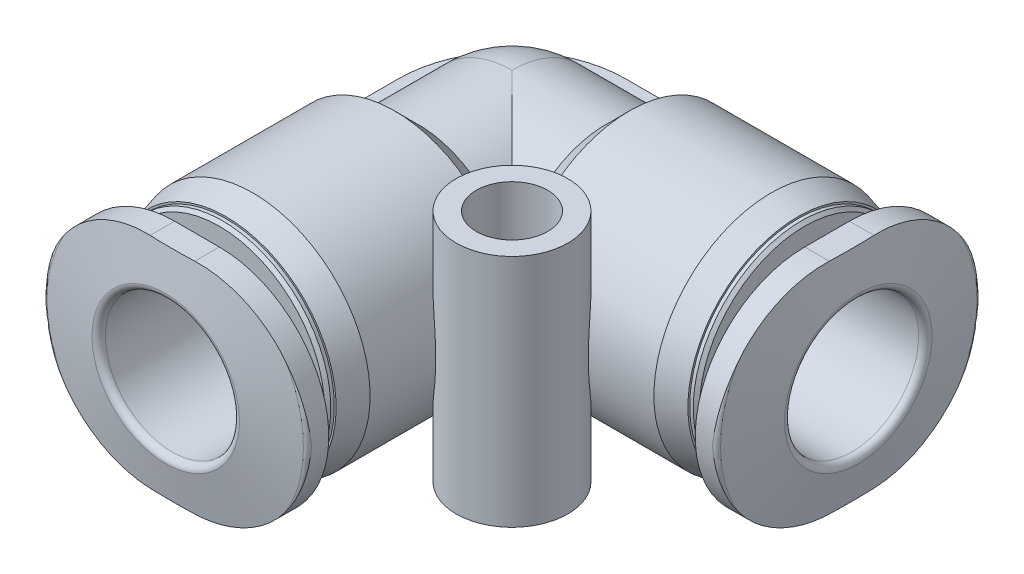
SolidWorks part; units mm, degrees
ref_plane "Ebene vorne" through (0, 0, 0) normal (0, 0, 1) x (1, 0, 0)
ref_plane "Ebene oben" through (0, 0, 0) normal (0, 1, 0) x (1, 0, 0)
ref_plane "Ebene rechts" through (0, 0, 0) normal (1, 0, 0) x (0, 0, -1)
sketch "Skizze1" plane through (0, 0, 0) normal (0, 0, 1) x (1, 0, 0)
  line L0 (0, 4.2) -> (4.2, 4.2)
  line L1 (4.2, 4.2) -> (5.25, 5.25)
  line L2 (5.25, 5.25) -> (11.6, 5.25)
  line L3 (11.6, 5.25) -> (12.8, 4.9285)
  line L4 (12.8, 4.9285) -> (12.8, 4.8481)
  line L5 (12.8, 4.8481) -> (12.9586, 4.8481)
  line L6 (12.9586, 4.8481) -> (13.1, 4.7067)
  line L7 (13.1, 4.7067) -> (13.1, 3.7)
  line L8 (13.1, 3.7) -> (13.73, 3.7)
  line L9 (14.1, 4.07) -> (14.1, 5.9)
  line L10 (14.1, 5.9) -> (14.8737, 5.9)
  line L11 (15.0707, 5.7347) -> (15.5, 3.3)
  line L12 (15.5, 3.3) -> (15.5, 0)
  line L13 (15.5, 0) -> (-4.2, 0)
  line L14 (15.5, 0) -> (-4.2, 0) construction
  arc A0 (-4.2, 0) -> (0, 4.2) centre (0, 0) cw
  arc A1 (13.73, 3.7) -> (14.1, 4.07) centre (13.73, 4.07) ccw
  arc A2 (14.8737, 5.9) -> (15.0707, 5.7347) centre (14.8737, 5.7) cw
revolve "Rotation1" add sketch "Skizze1" angle 360 about L14
ref_plane "Ebene1" through (15.5, 0, 0) normal (1, 0, 0) x (0, 0, -1)
sketch "Skizze2" plane through (15.5, 0, 0) normal (1, 0, 0) x (0, 0, -1)
  line L0 (-7.08, -4.0876) -> (0, -8.1753)
  line L1 (0, -8.1753) -> (7.08, -4.0876)
  line L2 (7.08, -4.0876) -> (7.08, 4.0876)
  line L3 (7.08, 4.0876) -> (0, 8.1753)
  line L4 (0, 8.1753) -> (-7.08, 4.0876)
  line L5 (-7.08, 4.0876) -> (-7.08, -4.0876)
  line L6 (-1, -4.9) -> (1, -4.9)
  line L7 (1, 4.9) -> (-1, 4.9)
  arc A0 (-5.9, 0) -> (-1, -4.9) centre (-1, 0) ccw
  arc A1 (1, -4.9) -> (5.9, 0) centre (1, 0) ccw
  arc A2 (5.9, 0) -> (1, 4.9) centre (1, 0) ccw
  arc A3 (-1, 4.9) -> (-5.9, 0) centre (-1, 0) ccw
extrude "Schnitt-Linear austragen1" cut sketch "Skizze2" against normal blind 1.4
sketch "Skizze3" plane through (0, 0, 0) normal (1, 0, 0) x (0, 0, -1)
  line L0 (-5.0779, -1.3333) -> (5.0779, -1.3333)
  line L1 (5.0779, 1.3333) -> (-5.0779, 1.3333)
  arc A0 (-5.0779, 1.3333) -> (-5.0779, -1.3333) centre (0, 0) ccw
  arc A1 (5.0779, -1.3333) -> (5.0779, 1.3333) centre (0, 0) ccw
extrude "Aufsatz-Linear austragen1" add sketch "Skizze3" along normal blind 5.25
sketch "Skizze4" plane through (0, 0, 0) normal (0, 1, 0) x (1, 0, 0)
  line L0 (0, 2) -> (3.5, 2)
  line L1 (3.5, 2) -> (3.5, 2.8)
  line L2 (3.7, 3) -> (15.2, 3)
  line L3 (15.5, 3.3) -> (15.5, 0)
  line L4 (15.5, 0) -> (-2, 0)
  line L5 (15.5, 0) -> (-2, 0) construction
  arc A0 (-2, 0) -> (0, 2) centre (0, 0) cw
  arc A1 (3.5, 2.8) -> (3.7, 3) centre (3.7, 2.8) cw
  arc A2 (15.2, 3) -> (15.5, 3.3) centre (15.2, 3.3) ccw
sketch "Skizze5" plane through (0, 0, 0) normal (0, 0, 1) x (1, 0, 0)
  line L0 (-5.0779, -1.3333) -> (0, -1.3333)
  line L1 (0, -1.3333) -> (0, 1.3333)
  line L2 (0, 1.3333) -> (-5.0779, 1.3333)
  arc A0 (-5.0779, 1.3333) -> (-5.0779, -1.3333) centre (0, 0) ccw
extrude "Aufsatz-Linear austragen2" add sketch "Skizze5" along normal blind 5.25
sketch "Skizze6" plane through (0, 0, 0) normal (1, 0, 0) x (0, 0, -1)
  line L0 (0, 0) -> (0, -4.2)
  line L1 (0, -4.2) -> (-4.2, -4.2)
  line L2 (-4.2, -4.2) -> (-5.25, -5.25)
  line L3 (-5.25, -5.25) -> (-11.6, -5.25)
  line L4 (-11.6, -5.25) -> (-12.8, -4.9285)
  line L5 (-12.8, -4.9285) -> (-12.8, -4.8481)
  line L6 (-12.8, -4.8481) -> (-12.9586, -4.8481)
  line L7 (-12.9586, -4.8481) -> (-13.1, -4.7067)
  line L8 (-13.1, -4.7067) -> (-13.1, -3.7)
  line L9 (-13.1, -3.7) -> (-13.73, -3.7)
  line L10 (-14.1, -4.07) -> (-14.1, -5.9)
  line L11 (-14.1, -5.9) -> (-14.8737, -5.9)
  line L12 (-15.0707, -5.7347) -> (-15.5, -3.3)
  line L13 (-15.5, -3.3) -> (-15.5, 0)
  line L14 (-15.5, 0) -> (0, 0)
  line L15 (-15.5, 0) -> (0, 0) construction
  arc A0 (-13.73, -3.7) -> (-14.1, -4.07) centre (-13.73, -4.07) ccw
  arc A1 (-14.8737, -5.9) -> (-15.0707, -5.7347) centre (-14.8737, -5.7) cw
revolve "Rotation2" add sketch "Skizze6" angle 360 about L15 reverse direction yes
ref_plane "Ebene2" through (0, 0, 15.5) normal (0, 0, 1) x (1, 0, 0)
sketch "Skizze7" plane through (0, 0, 15.5) normal (0, 0, 1) x (1, 0, 0)
  line L0 (-7.08, -4.0876) -> (0, -8.1753)
  line L1 (0, -8.1753) -> (7.08, -4.0876)
  line L2 (7.08, -4.0876) -> (7.08, 4.0876)
  line L3 (7.08, 4.0876) -> (0, 8.1753)
  line L4 (0, 8.1753) -> (-7.08, 4.0876)
  line L5 (-7.08, 4.0876) -> (-7.08, -4.0876)
  line L6 (-1, -4.9) -> (1, -4.9)
  line L7 (1, 4.9) -> (-1, 4.9)
  arc A0 (-5.9, 0) -> (-1, -4.9) centre (-1, 0) ccw
  arc A1 (1, -4.9) -> (5.9, 0) centre (1, 0) ccw
  arc A2 (5.9, 0) -> (1, 4.9) centre (1, 0) ccw
  arc A3 (-1, 4.9) -> (-5.9, 0) centre (-1, 0) ccw
extrude "Schnitt-Linear austragen2" cut sketch "Skizze7" against normal blind 1.4
sketch "Skizze8" plane through (0, 0, 0) normal (1, 0, 0) x (0, 0, -1)
  line L0 (0, 0) -> (0, -2)
  line L1 (0, -2) -> (-3.5, -2)
  line L2 (-3.5, -2) -> (-3.5, -2.8)
  line L3 (-3.7, -3) -> (-15.2, -3)
  line L4 (-15.5, -3.3) -> (-15.5, 0)
  line L5 (-15.5, 0) -> (0, 0)
  line L6 (-15.5, 0) -> (0, 0) construction
  arc A0 (-3.5, -2.8) -> (-3.7, -3) centre (-3.7, -2.8) cw
  arc A1 (-15.2, -3) -> (-15.5, -3.3) centre (-15.2, -3.3) ccw
sketch "Skizze9" plane through (0, 0, 0) normal (0, 1, 0) x (1, 0, 0)
  circle A0 centre (6.5, -6.5) radius 2.5
extrude "Aufsatz-Linear austragen3" add sketch "Skizze9" against normal blind 5.25 and the other way blind 5.25
hole_wizard "Bohrung1" positions "Skizze11" profile "Skizze10" legacy
sketch "Skizze11" plane through (0, 5.25, 0) normal (0, 1, 0) x (1, 0, 0)
  point P0 (6.5, -6.5)
sketch "Skizze10" plane through (6.5, 5.25, 6.5) normal (1, 0, 0) x (0, 0, 1)
  line L0 (0, 0) -> (0, 11.5)
  line L1 (0, 11.5) -> (1.6, 11.5)
  line L2 (1.6, 11.5) -> (1.6, 0)
  line L3 (1.6, 0) -> (0, 0)
  line L4 (0, 110) -> (0, -10) construction
  dimension "Durchmesser" = 3.2
  dimension "Tiefe" = 11.5
sketch "Skizze12" plane through (0, 0, 0) normal (1, 0, 0) x (0, 0, -1)
  line L0 (0, 1.3333) -> (5.0779, 1.3333)
  line L1 (5.0779, -1.3333) -> (0, -1.3333)
  line L2 (0, -1.3333) -> (0, 1.3333)
  line L3 (0, -1.3333) -> (0, 1.3333) construction
  arc A0 (5.0779, 1.3333) -> (5.0779, -1.3333) centre (0, 0) cw
revolve "Rotation3" add sketch "Skizze12" angle 90 about L3
revolve "Schnitt-Rotation1" cut sketch "Skizze8" angle 360 about L6 reverse direction yes
revolve "Schnitt-Rotation2" cut sketch "Skizze4" angle 360 about L5 reverse direction yes
